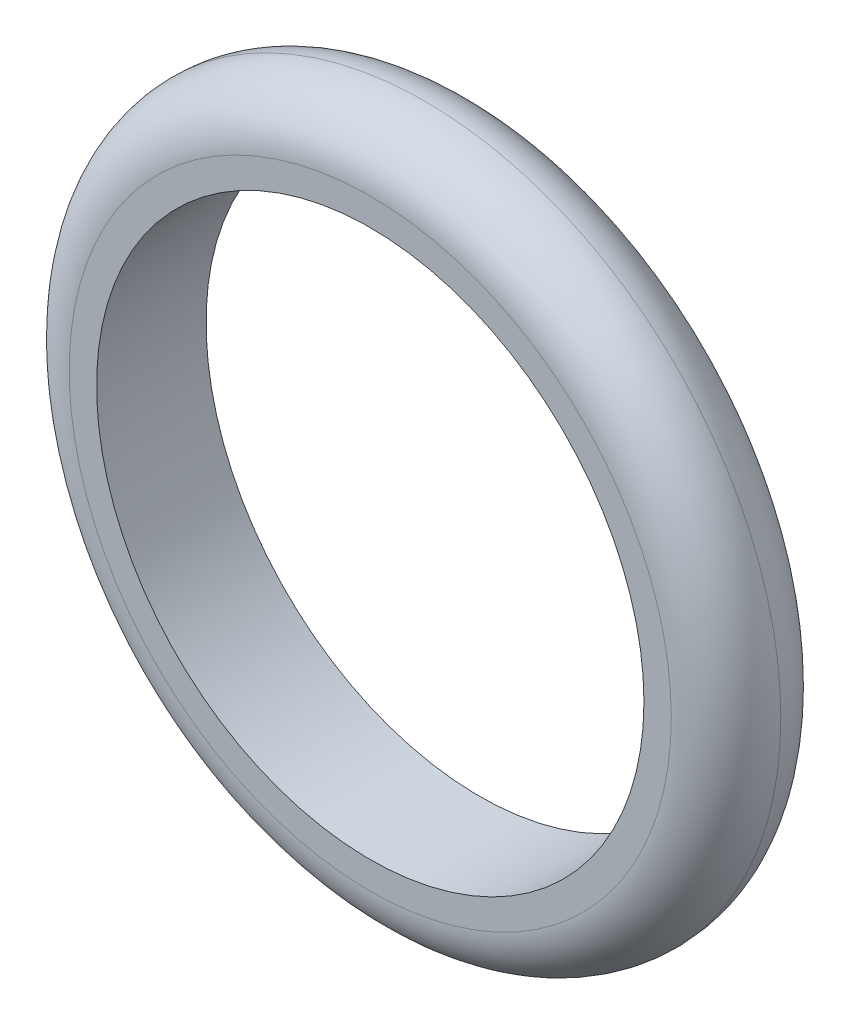
SolidWorks part; units mm, degrees
ref_plane "Front Plane" through (0, 0, 0) normal (0, 0, 1) x (1, 0, 0)
ref_plane "Top Plane" through (0, 0, 0) normal (0, 1, 0) x (1, 0, 0)
ref_plane "Right Plane" through (0, 0, 0) normal (1, 0, 0) x (0, 0, -1)
sketch "Sketch1" plane through (0, 0, 0) normal (0, 0, 1) x (1, 0, 0)
  circle A0 centre (0, 0) radius 3.25
  circle A1 centre (0, 0) radius 2.5
  dimension "D1" = 6.5
  dimension "D2" = 5
extrude "Boss-Extrude2" add sketch "Sketch1" along normal blind 1
fillet "Fillet1" radius 0.5 1 edges at (3.25, 0, 0)
fillet "Fillet2" radius 0.5 1 edges at (3.25, 0, 1)
